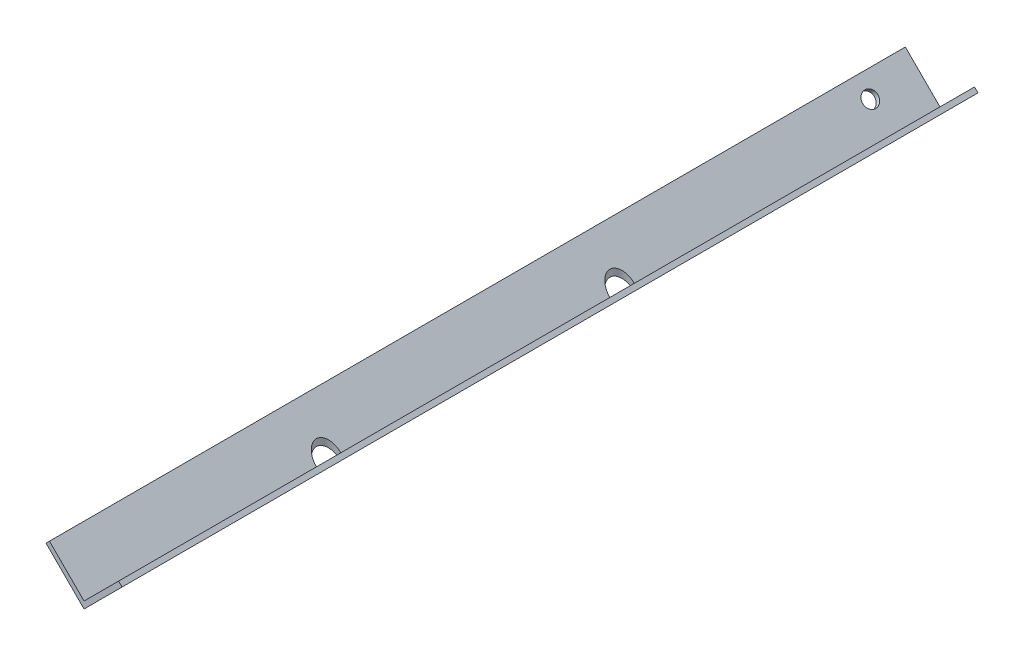
SolidWorks part; units mm, degrees
material "6061 Alloy"
ref_plane "Front Plane" through (0, 0, 0) normal (0, 0, 1) x (1, 0, 0)
ref_plane "Top Plane" through (0, 0, 0) normal (0, 1, 0) x (1, 0, 0)
ref_plane "Right Plane" through (0, 0, 0) normal (1, 0, 0) x (0, 0, -1)
sketch "Sketch1" plane through (0, 0, 0) normal (0, 0, 1) x (1, 0, 0)
  line L0 (0, 0) -> (-8.9803, 8.9803)
  line L1 (-8.9803, 8.9803) -> (-9.8783, 8.0822)
  line L2 (-9.8783, 8.0822) -> (0, -1.7961)
  line L3 (0, -1.7961) -> (9.8783, 8.0822)
  line L4 (9.8783, 8.0822) -> (8.9803, 8.9803)
  line L5 (8.9803, 8.9803) -> (0, 0)
  line L6 (-13.872, 0) -> (16.6117, 0) construction
  dimension "D1" = 1.27
  dimension "D2" = 12.7
extrude "Boss-Extrude1" add sketch "Sketch1" along normal blind 222.25
sketch "Sketch2" plane through (0, 0, 0) normal (-0.7071, 0.7071, 0) x (0, 0, 1)
  line L0 (222.25, 12.7) -> (0, 12.7) construction
  line L1 (0, 12.7) -> (0, 0) construction
  circle A0 centre (6.35, 7.62) radius 1.9844
  circle A1 centre (19.05, 7.62) radius 1.9844
  dimension "D4" = 3.9688
  dimension "D1" = 5.08
  dimension "D2" = 5.08
  dimension "D3" = 6.35
  dimension "D5" = 19.05
sketch "Sketch3" plane through (0, 0, 0) normal (0.7071, 0.7071, 0) x (0, 0, -1)
  line L0 (0, 0) -> (0, 12.7) construction
  line L1 (-222.25, 12.7) -> (0, 12.7) construction
  circle A0 centre (-12.7, 7.62) radius 1.9844
  dimension "D3" = 3.9688
  dimension "D1" = 12.7
  dimension "D2" = 5.08
extrude "Cut-Extrude1" cut sketch "Sketch2" against normal through all
extrude "Cut-Extrude2" cut sketch "Sketch3" against normal through all
sketch "Sketch4" plane through (0, 0, 0) normal (0, 1, 0) x (1, 0, 0)
  line L0 (0, -5.927) -> (0, 5.927) construction
  line L1 (8.9803, -222.25) -> (0, -222.25) construction
  circle A0 centre (0, -158.75) radius 3.175
  circle A1 centre (0, -82.55) radius 3.175
  dimension "D1" = 6.35
  dimension "D2" = 6.35
  dimension "D3" = 76.2
  dimension "D4" = 63.5
extrude "Cut-Extrude4" cut sketch "Sketch4" against normal through all both and the other way through all
